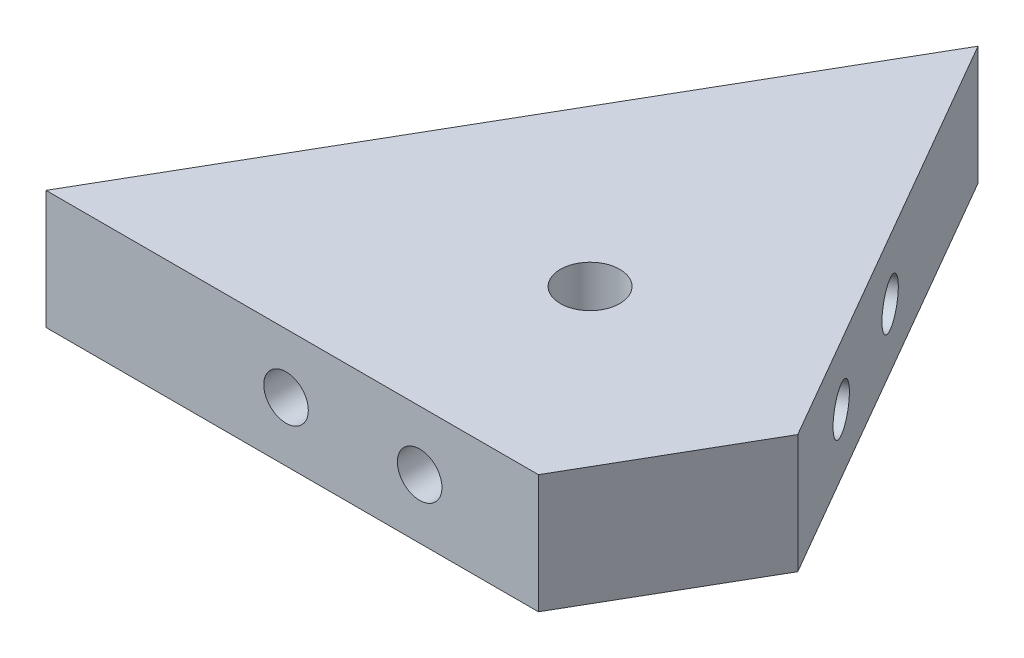
SolidWorks part; units mm, degrees
material "1023 Carbon Steel Sheet (SS)"
ref_plane "Front Plane" through (0, 0, 0) normal (0, 0, 1) x (1, 0, 0)
ref_plane "Top Plane" through (0, 0, 0) normal (0, 1, 0) x (1, 0, 0)
ref_plane "Right Plane" through (0, 0, 0) normal (1, 0, 0) x (0, 0, -1)
sketch "Sketch1" plane through (0, 0, 0) normal (0, 1, 0) x (1, 0, 0)
  line L0 (159.6594, -241.1624) -> (-297.5406, 22.8022) construction
  line L1 (-145.1406, 286.7667) -> (-449.9406, -241.1624) construction
  line L2 (-449.9406, -241.1624) -> (159.6594, -241.1624) construction
  line L3 (159.6594, -241.1624) -> (-145.1406, 286.7667) construction
  line L4 (93.6683, -241.1624) -> (93.6683, -203.0624) construction
  line L5 (119.0683, -241.1624) -> (129.2161, -223.5859)
  line L6 (65.0933, -241.1624) -> (65.0933, -186.5646) construction
  line L7 (13.7669, -241.1624) -> (50.24, -177.9891)
  line L8 (13.7669, -241.1624) -> (119.0683, -241.1624)
  line L9 (50.24, -177.9891) -> (129.2161, -223.5859)
  line L10 (93.6683, -203.0624) -> (65.0933, -203.0624) construction
  dimension "D1" = 609.6
  dimension "D2" = 38.1
  dimension "D3" = 25.4
  dimension "D4" = 28.575
  dimension "D6" = 40.5911
  dimension "D5" = 25.4
extrude "Boss-Extrude1" add sketch "Sketch1" along normal blind 25.4
sketch "Sketch2" plane through (0, 0, 241.1624) normal (0, 0, 1) x (1, 0, 0)
  line L0 (13.7669, 0) -> (119.0683, 0) construction
  line L1 (13.7669, 0) -> (13.7669, 25.4) construction
  line L2 (119.0683, 0) -> (119.0683, 25.4) construction
  line L3 (13.7669, 25.4) -> (119.0683, 25.4) construction
  line L4 (13.7669, 0) -> (119.0683, 25.4) construction
  line L5 (119.0683, 0) -> (13.7669, 25.4) construction
  line L6 (93.6683, 25.4) -> (93.6683, 0) construction
  line L7 (65.0933, 0) -> (65.0933, 25.4) construction
  circle A0 centre (65.0933, 12.7) radius 4.7625
  circle A1 centre (93.6683, 12.7) radius 4.7625
  point P6 (66.4176, 12.7)
  dimension "D4" = 9.525
  dimension "D5" = 9.525
  dimension "D1" = 25.4
  dimension "D2" = 25.4
  dimension "D3" = 28.575
extrude "Cut-Extrude1" cut sketch "Sketch2" against normal blind 12.7
sketch "Sketch3" plane through (0, 0, 228.4624) normal (0, 0, 1) x (1, 0, 0)
  circle A0 centre (65.0933, 12.7) radius 3.9687
  dimension "D1" = 7.9375
extrude "Cut-Extrude2" cut sketch "Sketch3" against normal blind 12.7
sketch "Sketch4" plane through (0, 0, 228.4624) normal (0, 0, 1) x (1, 0, 0)
  circle A0 centre (93.6683, 12.7) radius 3.9688
  dimension "D1" = 7.9375
extrude "Cut-Extrude3" cut sketch "Sketch4" against normal blind 12.7
mirror "Mirror1" about plane through (50.24, 25.4, 177.9891) normal (-0.5, 0, 0.866) of "Boss-Extrude1", "Cut-Extrude1", "Cut-Extrude2", "Cut-Extrude3"
sketch "Sketch5" plane through (0, 25.4, 0) normal (0, 1, 0) x (1, 0, 0)
  line L0 (86.7131, -114.8157) -> (13.7669, -241.1624) construction
  line L1 (13.7669, -241.1624) -> (119.0683, -241.1624) construction
  line L2 (119.0683, -241.1624) -> (139.3639, -206.0094) construction
  line L3 (139.3639, -206.0094) -> (86.7131, -114.8157) construction
  line L4 (50.24, -177.9891) -> (129.2161, -223.5859) construction
  circle A0 centre (89.728, -200.7875) radius 6.35
  dimension "D1" = 12.7
extrude "Cut-Extrude4" cut sketch "Sketch5" against normal through all
equation "\"bplate_length\"= 24in"
equation "\"bplate_height\"= 6in"
equation "\"bplate_thickness\"= 0.5in"
equation "\"connector_plate_hole_diameter\"= 0.375in"
equation "\"connector_plate_hole_depth\"= 1in"
equation "\"connector_plate_thickness\"= 1in"
equation "\"D1@Sketch1\"=\"bplate_length\""
